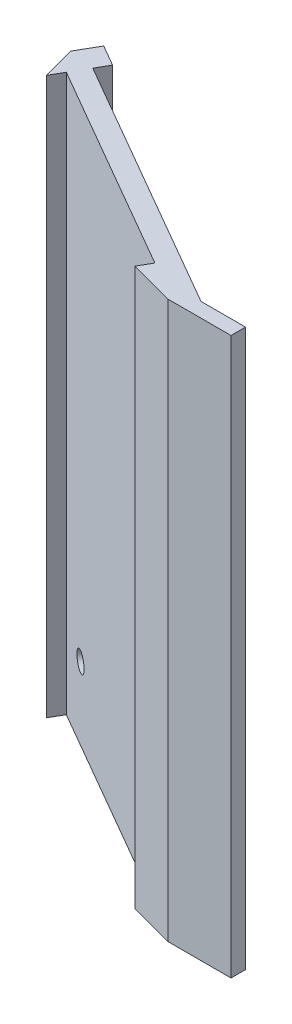
SolidWorks part; units mm, degrees
ref_plane "Plan de face" through (0, 0, 0) normal (0, 0, 1) x (1, 0, 0)
ref_plane "Plan de dessus" through (0, 0, 0) normal (0, 1, 0) x (1, 0, 0)
ref_plane "Plan de droite" through (0, 0, 0) normal (1, 0, 0) x (0, 0, -1)
sketch "Esquisse1" plane through (0, 0, 0) normal (0, 1, 0) x (1, 0, 0)
  line L0 (161.1651, -2.9953) -> (-1.8349, -2.9953) construction
  line L1 (-11.1651, -0.4953) -> (-1.8349, -2.9953)
  line L2 (-1.8349, -2.9953) -> (11.1651, -2.9953)
  line L3 (11.1651, -2.9953) -> (11.1651, 0.0047)
  line L4 (11.1651, 0.0047) -> (1.9689, 0.0047)
  line L5 (-55.2965, 33.0669) -> (-53.7965, 35.6649)
  line L7 (-11.1651, -0.4953) -> (-9.6651, 2.1028)
  line L8 (-54.4663, 24.5047) -> (-56.2965, 31.3348)
  line L9 (-9.6651, 2.1028) -> (-52.9663, 27.1028)
  line L11 (-7.6601, 5.564) -> (-50.9663, 30.5669)
  line L12 (-56.2965, 31.3348) -> (-55.2965, 33.0669)
  line L13 (-54.4663, 24.5047) -> (-52.9663, 27.1028)
  line L14 (-53.7965, 35.6649) -> (-49.4663, 33.1649)
  line L15 (-7.6601, 5.564) -> (1.9689, 0.0047)
  line L16 (-49.4663, 33.1649) -> (-50.9663, 30.5669)
  dimension "D1" = 7
  dimension "D2" = 5
  dimension "D3" = 5
extrude "Boss.-Extru.1" add sketch "Esquisse1" along normal blind 115 contours L4 L1 L2 L3 region at (-24.8594, 0, -13.4483)
sketch "Esquisse3" plane through (-1.5057, 0, 2.608) normal (-0.5, 0, 0.866) x (0.866, 0, 0.5)
  line L0 (-59.4216, 115) -> (-59.4216, 0) construction
  line L1 (-9.4216, 115) -> (-9.4216, 0) construction
  line L2 (-9.4216, 0) -> (-59.4216, 0) construction
  circle A0 centre (-51.4216, 15) radius 2
  circle A1 centre (-17.4216, 15) radius 2
  dimension "D1" = 4
  dimension "D2" = 8
  dimension "D3" = 8
  dimension "D4" = 15
extrude "Enlèv. mat.-Extru.1" cut sketch "Esquisse3" against normal blind 115
sketch "Esquisse4" plane through (0.4943, 0, -0.8561) normal (0.5, 0, -0.866) x (-0.866, 0, -0.5)
  line L0 (59.4216, 0) -> (-1.7028, 0) construction
  line L1 (19.731, 11) -> (22.0404, 15)
  line L2 (22.0404, 15) -> (19.731, 19)
  line L3 (19.731, 19) -> (15.1122, 19)
  line L4 (15.1122, 19) -> (12.8028, 15)
  line L5 (12.8028, 15) -> (15.1122, 11)
  line L6 (15.1122, 11) -> (19.731, 11)
  line L7 (49.1122, 11) -> (53.731, 11)
  line L8 (53.731, 11) -> (56.0404, 15)
  line L9 (56.0404, 15) -> (53.731, 19)
  line L10 (53.731, 19) -> (49.1122, 19)
  line L11 (49.1122, 19) -> (46.8028, 15)
  line L12 (46.8028, 15) -> (49.1122, 11)
  line L13 (9.4216, 0) -> (25.4216, 0)
  line L14 (9.4216, 0) -> (9.4216, 22)
  line L15 (9.4216, 22) -> (25.4216, 22)
  line L16 (25.4216, 0) -> (25.4216, 22)
  line L17 (9.4216, 0) -> (25.4216, 22) construction
  line L18 (9.4216, 22) -> (25.4216, 0) construction
  line L19 (59.4216, 115) -> (59.4216, 0) construction
  line L20 (43.4216, 0) -> (59.4216, 0)
  line L21 (43.4216, 0) -> (43.4216, 22)
  line L22 (43.4216, 22) -> (59.4216, 22)
  line L23 (59.4216, 0) -> (59.4216, 22)
  line L24 (43.4216, 0) -> (59.4216, 22) construction
  line L25 (43.4216, 22) -> (59.4216, 0) construction
  circle A0 centre (17.4216, 15) radius 4 construction
  circle A1 centre (51.4216, 15) radius 4 construction
  point P23 (17.4216, 11)
  point P29 (51.4216, 11)
  dimension "D1" = 8
  dimension "D2" = 8
  dimension "D3" = 22
  dimension "D4" = 8
  dimension "D5" = 16
  dimension "D6" = 8
extrude "Boss.-Extru.2" add sketch "Esquisse4" along normal up to surface (3 mm away) up to face at (-51.6314, 57.5, -34.4149)
fillet "Congé1" radius 3.5 6 edges at (-21.5215, 11, -13.5669) (-7.6651, 11, -5.5669) (-14.5933, 22, -9.5669) (-37.1099, 11, -22.5669) (-44.0381, 22, -26.5669) (-50.2163, 22, -31.8659)
